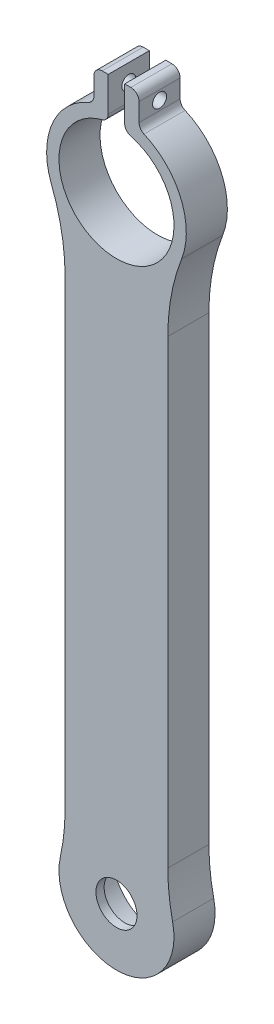
SolidWorks part; units mm, degrees
ref_plane "Front Plane" through (0, 0, 0) normal (0, 0, 1) x (1, 0, 0)
ref_plane "Top Plane" through (0, 0, 0) normal (0, 1, 0) x (1, 0, 0)
ref_plane "Right Plane" through (0, 0, 0) normal (1, 0, 0) x (0, 0, -1)
sketch "Sketch2" plane through (0, 0, 0) normal (0, 0, 1) x (1, 0, 0)
  line L0 (2, 163.8564) -> (2, 173.8564)
  line L1 (-14, 0) -> (14, 0)
  line L5 (2, 173.8564) -> (5.5, 173.8564)
  line L6 (5.5, 173.8564) -> (5.5, 166.0857)
  line L7 (-2, 163.8564) -> (-2, 173.8564)
  line L8 (0, -55) -> (0, 55) construction
  line L9 (-2, 173.8564) -> (-5.5, 173.8564)
  line L10 (-5.5, 173.8564) -> (-5.5, 166.0857)
  line L12 (-12.5, 6.3048) -> (-12.5, 138.4783)
  line L13 (12.5, 6.3048) -> (12.5, 138.4783)
  circle A0 centre (0, 0) radius 14
  circle A1 centre (0, 150) radius 14
  circle A2 centre (0, 0) radius 11
  arc A5 (-14, 0) -> (-12.5, 6.3048) centre (0, 0) cw
  arc A6 (14, 0) -> (12.5, 6.3048) centre (0, 0) ccw
  circle A9 centre (0, 150) radius 17
  dimension "D1" = 28
  dimension "D3" = 22
  dimension "D4" = 28
  dimension "D6" = 2
  dimension "D8" = 10
  dimension "D5" = 34
  dimension "D2" = 150
  dimension "D7" = 3.5
  dimension "D9" = 25
extrude "Boss-Extrude1" add sketch "Sketch2" along normal blind 10 contours A9 L6 L5 L0 | A9 L7 L9 L10 | A9 A1 | A9 L12 A0 L13 | A2 L1 A0 | A2 L1 A0 region at (2.48, 165.3692, 0) region at (3.7817, 170.199, 0) region at (-3.7817, 170.199, 0) region at (0, 73.2388, 0) region at (13.3153, 3.1679, 0) region at (0, -13.687, 0)
sketch "Sketch6" plane through (0, 0, 10) normal (0, 0, -1) x (-1, 0, 0)
  circle A0 centre (0, 0) radius 5
  circle A1 centre (0, 0) radius 11 construction
  circle A2 centre (0, 0) radius 11
  dimension "D1" = 10
extrude "Boss-Extrude3" add sketch "Sketch6" along normal blind 2
fillet "Fillet1" radius 2 6 edges at (-5.5, 173.8564, 5) (5.5, 173.8564, 5) (5.5, 166.0857, 5) (2, 163.8564, 5) (-2, 163.8564, 5) (-5.5, 166.0857, 5)
sketch "Sketch11" plane through (0, 0, 0) normal (0, 0, -1) x (-1, 0, 0)
  line L1 (-10.5, 130) -> (10.5, 130)
  line L2 (-10.5, 130) -> (-10.5, 20)
  line L3 (-10.5, 20) -> (10.5, 20)
  line L4 (10.5, 130) -> (10.5, 20)
  line L6 (-12.5, 6.3048) -> (-12.5, 138.4783) construction
  line L7 (12.5, 6.3048) -> (12.5, 138.4783) construction
  arc A1 (-3.5, 163.5554) -> (3.5, 163.5554) centre (0, 150) ccw construction
  dimension "D4" = 110
  dimension "D3" = 20
  dimension "D1" = 2
  dimension "D2" = 2
extrude "Cut-Extrude1" cut sketch "Sketch11" against normal offset from surface (8 mm away) 2 up to face at (0, 144.8911, 10)
fillet "Fillet2" radius 50 4 edges at (-12.5, 6.3048, 5) (12.5, 6.3048, 5) (-12.5, 138.4783, 5) (12.5, 138.4783, 5)
sketch "Sketch12" plane through (5.5, 0, 0) normal (1, 0, 0) x (0, 0, -1)
  line L0 (0, 171.8564) -> (-10, 171.8564) construction
  line L1 (0, 171.8564) -> (0, 167.4571) construction
  point P0 (-5, 169.6567)
  point P3 (-5, 171.8564)
  point P6 (0, 169.6567)
hole_wizard "M3 Clearance Hole1" positions "Sketch13" profile "Sketch14" hole size "M3" standard "ANSI Metric" end condition through all
sketch "Sketch13" plane through (5.5, 0, 0) normal (1, 0, 0) x (0, 0, -1)
  point P0 (-5, 169.6567)
sketch "Sketch14" plane through (5.5, 169.6567, 5) normal (0, 1, 0) x (0, 0, -1)
  line L0 (0, 0) -> (0, 22.5)
  line L1 (0, 22.5) -> (1.7, 22.5)
  line L2 (1.7, 22.5) -> (1.7, 0)
  line L5 (1.7, 0) -> (0, 0)
  line L11 (0, -6.35) -> (0, 107.95) construction
  dimension "Thru Hole Dia." = 3.4
  dimension "Thru Hole Depth" = 22.5
fillet "Fillet3" radius 2 6 edges at (-10.5, 130, 4) (10.5, 130, 4) (0, 20, 0) (-10.5, 75, 0) (10.5, 75, 0) (0, 130, 0)
